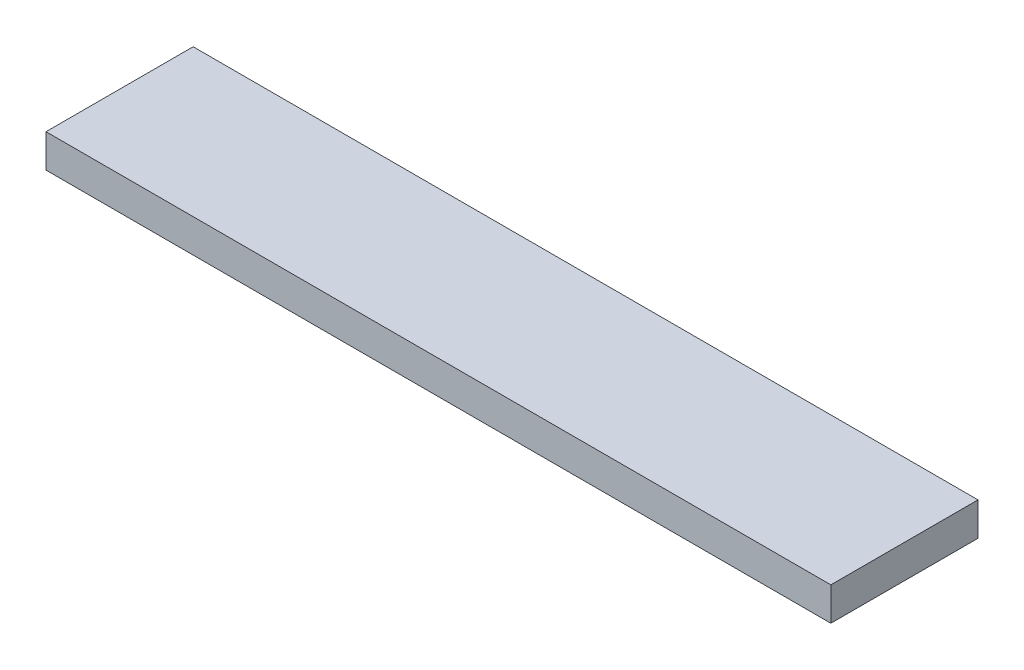
SolidWorks part; units mm, degrees
ref_plane "前视基准面" through (0, 0, 0) normal (0, 0, 1) x (1, 0, 0)
ref_plane "上视基准面" through (0, 0, 0) normal (0, 1, 0) x (1, 0, 0)
ref_plane "右视基准面" through (0, 0, 0) normal (1, 0, 0) x (0, 0, -1)
sketch "草图1" plane through (0, 0, 0) normal (0, 1, 0) x (1, 0, 0)
  line L1 (0, 42) -> (224, 42)
  line L2 (0, 42) -> (0, 0)
  line L3 (0, 0) -> (224, 0)
  line L4 (224, 42) -> (224, 0)
  dimension "D1" = 224
  dimension "D2" = 42
extrude "凸台-拉伸1" add sketch "草图1" along normal blind 9.5
